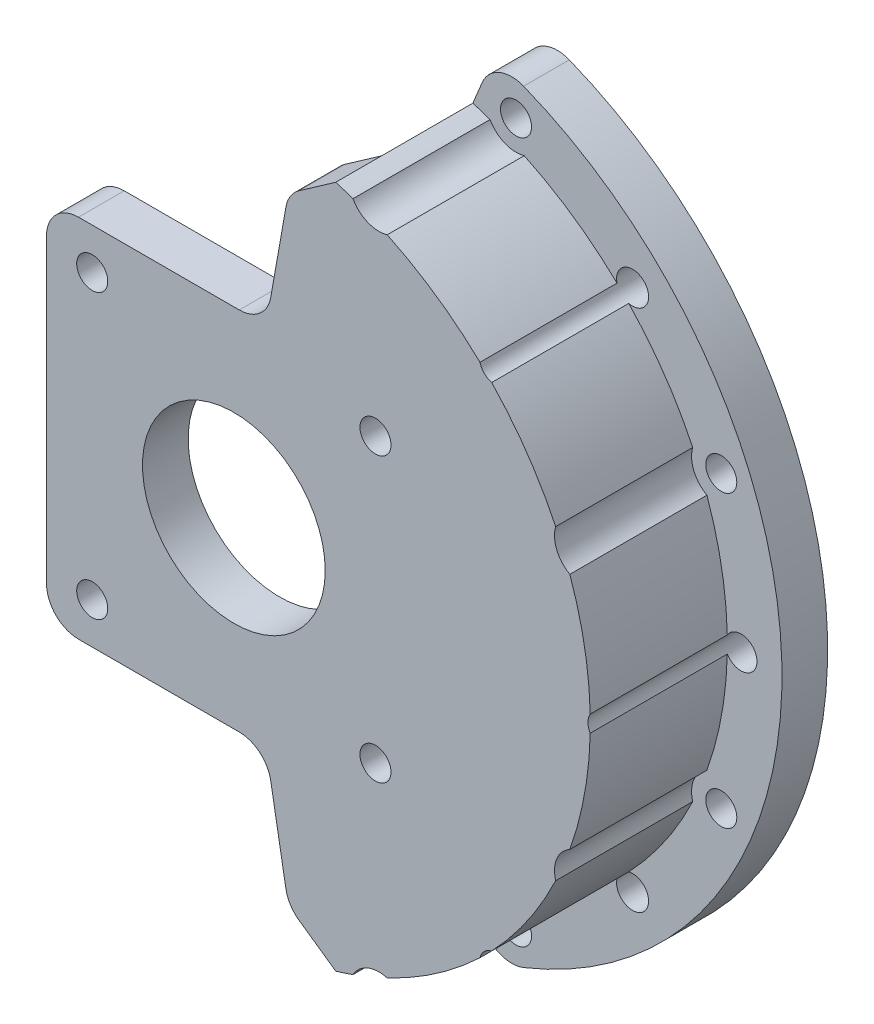
SolidWorks part; units mm, degrees
ref_plane "Alzado" through (0, 0, 0) normal (0, 0, 1) x (1, 0, 0)
ref_plane "Planta" through (0, 0, 0) normal (0, 1, 0) x (1, 0, 0)
ref_plane "Vista lateral" through (0, 0, 0) normal (1, 0, 0) x (0, 0, -1)
sketch "Croquis1" plane through (0, 0, 0) normal (0, 0, 1) x (1, 0, 0)
  line L0 (0, 0) -> (40.5, 0) construction
  line L1 (0, 0) -> (15.8814, 38.341) construction
  line L2 (13.4513, 42.9268) -> (10.7725, 36.4596)
  line L3 (0, 0) -> (38.341, 15.8814) construction
  line L4 (0, 0) -> (38.341, -15.8814) construction
  line L5 (0, 0) -> (15.8814, -38.341) construction
  line L6 (13.4513, -42.9268) -> (10.7725, -36.4596)
  circle A0 centre (0, 0) radius 40.5 construction
  circle A1 centre (15.8814, 38.341) radius 1.7
  circle A2 centre (0, 0) radius 41.5 construction
  circle A3 centre (0, 0) radius 41.5 construction
  circle A4 centre (38.341, 15.8814) radius 1.7
  circle A5 centre (0, 0) radius 41.5 construction
  circle A6 centre (38.341, -15.8814) radius 1.7
  circle A7 centre (0, 0) radius 41.5 construction
  circle A8 centre (15.8814, -38.341) radius 1.7
  arc A9 (10.7725, -36.4596) -> (10.7725, 36.4596) centre (0, 0) ccw
  arc A10 (13.4513, -42.9268) -> (13.4513, 42.9268) centre (0, 0) ccw
  point P9 (12.1119, 39.6932)
  point P22 (0, 0)
  dimension "D1" = 81
  dimension "D4" = 3.4
  dimension "D2" = 41.5
  dimension "D3" = 67.5
  dimension "D5" = 7
  dimension "D6" = 4
  dimension "D8" = 67.5
  dimension "D7" = 4
extrude "Saliente-Extruir1" add sketch "Croquis1" along normal blind 5
sketch "Croquis2" plane through (0, 0, 0) normal (0, 0, -1) x (-1, 0, 0)
  circle A0 centre (0, 0) radius 39.0124
extrude "Saliente-Extruir2" add sketch "Croquis2" against normal blind 20
sketch "Croquis3" plane through (0, 0, 20) normal (0, 0, 1) x (1, 0, 0)
  line L0 (0, 0) -> (-20.5, 0) construction
  line L1 (-15.5, -15.5) -> (15.5, -15.5) construction
  line L2 (-15.5, -15.5) -> (-15.5, 15.5) construction
  line L3 (-15.5, 15.5) -> (15.5, 15.5) construction
  line L4 (15.5, -15.5) -> (15.5, 15.5) construction
  line L5 (-15.5, -15.5) -> (15.5, 15.5) construction
  line L6 (-15.5, 15.5) -> (15.5, -15.5) construction
  line L7 (-20.5, 20) -> (-20.5, -20)
  line L8 (-20.5, 20) -> (3.5265, 20)
  line L9 (3.5265, 20) -> (6.7744, 38.4197)
  line L10 (3.5265, -20) -> (6.7744, -38.4197)
  line L11 (-20.5, -20) -> (3.5265, -20)
  circle A0 centre (-15.5, 15.5) radius 1.7
  circle A1 centre (15.5, 15.5) radius 1.7
  circle A2 centre (15.5, -15.5) radius 1.7
  circle A3 centre (-15.5, -15.5) radius 1.7
  circle A5 centre (0, 0) radius 39.0124 construction
  arc A6 (6.7744, 38.4197) -> (6.7744, -38.4197) centre (0, 0) ccw
  circle A7 centre (0, 0) radius 10
  point P0 (0, 0)
  point P16 (0, 0)
  point P18 (-20.5, 0)
  dimension "D3" = 3.4
  dimension "D6" = 20
  dimension "D2" = 31
  dimension "D4" = 40
  dimension "D5" = 20.5
  dimension "D7" = 100
  dimension "D1" = 4
extrude "Cortar-Extruir1" cut sketch "Croquis3" against normal blind 5
sketch "Croquis4" plane through (0, 0, 0) normal (0, 0, -1) x (-1, 0, 0)
  line L0 (-13.4513, 42.9268) -> (-11.1552, 37.3835)
  line L1 (-11.1552, 37.3835) -> (-9.8032, 34.1196)
  line L2 (0, 0) -> (35, 0) construction
  line L3 (-11.1552, -37.3835) -> (-9.8032, -34.1196)
  line L4 (-13.4513, -42.9268) -> (-11.1552, -37.3835)
  arc A0 (-9.8032, 34.1196) -> (-9.8032, -34.1196) centre (0, 0) ccw
  arc A1 (-13.4513, -42.9268) -> (-13.4513, 42.9268) centre (0, 0) ccw
  dimension "D1" = 71
extrude "Cortar-Extruir2" cut sketch "Croquis4" against normal blind 15
chamfer "Chaflán1" distance 4.75 angle 45 2 edges at (6.7744, 38.4197, 17.5) (6.7744, -38.4197, 17.5)
fillet "Redondeo2" radius 3.5 8 edges at (13.4513, -42.9268, 2.5) (13.4513, 42.9268, 2.5) (3.5265, 20, 17.5) (3.5265, -20, 17.5) (-20.5, -20, 17.5) (-20.5, 20, 17.5) (5.9496, -33.7419, 17.5) (5.9496, 33.7419, 17.5)
sketch "Croquis5" plane through (0, 0, 5) normal (0, 0, 1) x (1, 0, 0)
  circle A0 centre (15.8814, -38.341) radius 3.25
  dimension "D1" = 6.5
extrude "Cortar-Extruir3" cut sketch "Croquis5" along normal up to surface (15 mm away) up to face at (-13.8, -15.5, 20)
pattern_circular "MatrizC1" count 4 over 135 about axis through (0, 0, 20) along (0, 0, -1) of "Cortar-Extruir3" reverse direction yes
sketch "Croquis6" plane through (0, 0, 15) normal (0, 0, -1) x (-1, 0, 0)
  circle A0 centre (15.5, 15.5) radius 3.25
  circle A1 centre (15.5, -15.5) radius 3.25
  circle A2 centre (-15.5, -15.5) radius 3.25
  circle A3 centre (-15.5, 15.5) radius 3.25
  point P12 (0, 0)
  dimension "D1" = 6.5
  dimension "D2" = 4
extrude "Cortar-Extruir4" cut sketch "Croquis6" against normal blind 2.5
chamfer "Chaflán4" distance 2 angle 45 1 edges at (35.5, 0, 15)
sketch "Croquis8" plane through (0, 0, 0) normal (0, 0, -1) x (-1, 0, 0)
  line L0 (0, 0) -> (-50.5888, 0) construction
  line L5 (0, 0) -> (-38.341, -15.8814) construction
  circle A0 centre (-40.5, 0) radius 1.7 construction
  circle A1 centre (0, 0) radius 40.5 construction
  circle A2 centre (-28.6378, 28.6378) radius 1.7 construction
  circle A3 centre (0, 40.5) radius 1.7 construction
  circle A4 centre (28.6378, 28.6378) radius 1.7 construction
  circle A5 centre (40.5, 0) radius 1.7 construction
  circle A17 centre (-40.5, 0) radius 1.75
  circle A20 centre (-28.6378, -28.6378) radius 1.75
  circle A21 centre (-28.6378, 28.6378) radius 1.75
  point P17 (0, 0)
  dimension "D1" = 81
  dimension "D2" = 3.4
  dimension "D4" = 3.5
  dimension "D5" = 3.5
  dimension "D3" = 5
extrude "Cortar-Extruir5" cut sketch "Croquis8" against normal blind 32.5
